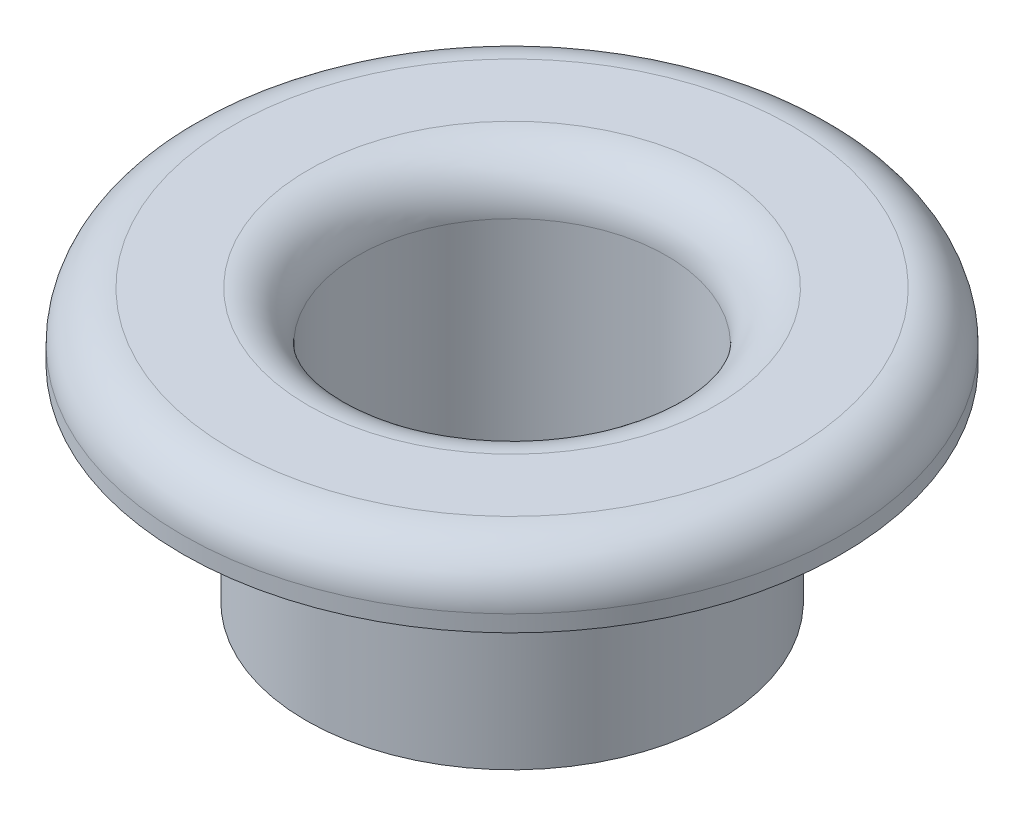
SolidWorks part; units mm, degrees
ref_plane "Front Plane" through (0, 0, 0) normal (0, 0, 1) x (1, 0, 0)
ref_plane "Top Plane" through (0, 0, 0) normal (0, 1, 0) x (1, 0, 0)
ref_plane "Right Plane" through (0, 0, 0) normal (1, 0, 0) x (0, 0, -1)
sketch "Sketch1" plane through (0, 0, 0) normal (0, 1, 0) x (1, 0, 0)
  circle A0 centre (0, 0) radius 2.3813
  circle A1 centre (0, 0) radius 3.175
  dimension "D1" = 4.7625
  dimension "D2" = 0.7937
extrude "Boss-Extrude1" add sketch "Sketch1" along normal blind 3.175
sketch "Sketch2" plane through (0, 3.175, 0) normal (0, 1, 0) x (1, 0, 0)
  circle A0 centre (0, 0) radius 5.08
  circle A1 centre (0, 0) radius 2.3813 construction
  circle A2 centre (0, 0) radius 2.3813
  dimension "D1" = 10.16
extrude "Boss-Extrude2" add sketch "Sketch2" along normal blind 1.016
fillet "Fillet1" radius 0.762 2 edges at (0, 4.191, 5.08) (0, 4.191, 2.3813)
